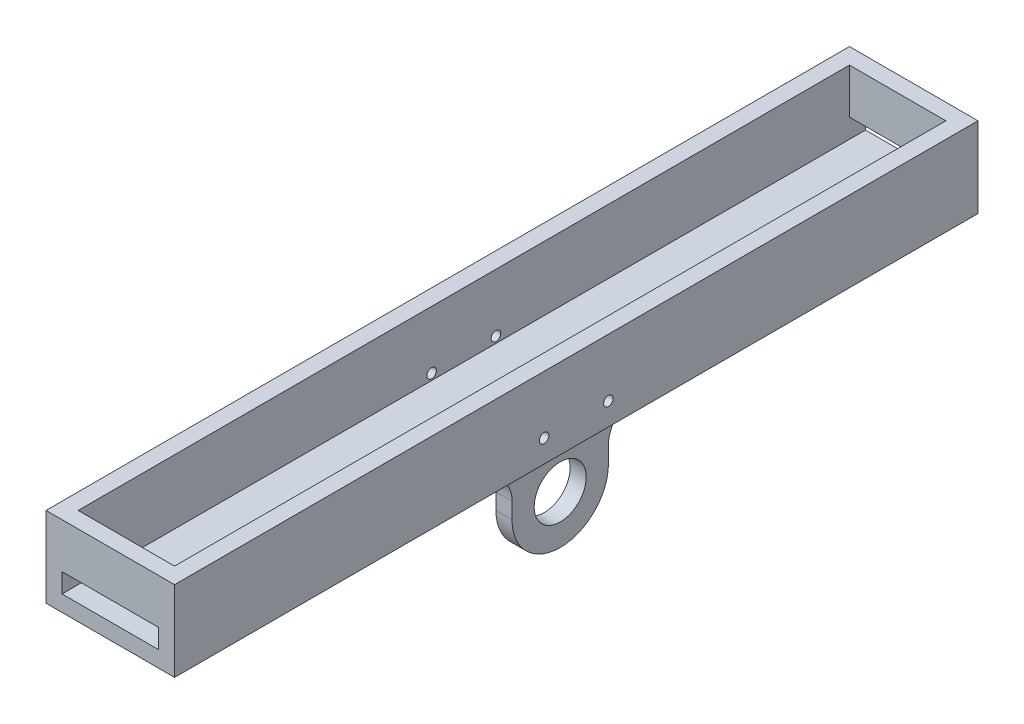
SolidWorks part; units mm, degrees
ref_plane "Front Plane" through (0, 0, 0) normal (0, 0, 1) x (1, 0, 0)
ref_plane "Top Plane" through (0, 0, 0) normal (0, 1, 0) x (1, 0, 0)
ref_plane "Right Plane" through (0, 0, 0) normal (1, 0, 0) x (0, 0, -1)
sketch "Sketch1" plane through (0, 0, 0) normal (0, 0, 1) x (1, 0, 0)
  line L0 (35, 25) -> (40, 25)
  line L1 (0, 0) -> (40, 0)
  line L2 (0, 0) -> (0, 25)
  line L3 (0, 25) -> (5, 25)
  line L4 (40, 0) -> (40, 25)
  line L6 (5, 25) -> (5, 5)
  line L7 (5, 5) -> (35, 5)
  line L8 (35, 25) -> (35, 5)
  dimension "D1" = 30
  dimension "D2" = 5
  dimension "D3" = 5
  dimension "D4" = 5
  dimension "D5" = 20
extrude "Boss-Extrude1" add sketch "Sketch1" along normal blind 250
sketch "Sketch2" plane through (40, 0, 0) normal (1, 0, 0) x (0, 0, -1)
  line L5 (-250, 0) -> (0, 0) construction
  line L6 (-140, -15) -> (-140, -10)
  line L7 (-110, -15) -> (-110, -10)
  line L10 (-150, 0) -> (-100, 0)
  circle A0 centre (-125, -15) radius 8.1
  arc A1 (-140, -15) -> (-110, -15) centre (-125, -15) ccw
  arc A2 (-110, -10) -> (-100, 0) centre (-100, -10) cw
  arc A3 (-140, -10) -> (-150, 0) centre (-150, -10) ccw
  point P4 (-125, 0)
  point P11 (-85, 0)
  point P14 (-115, 0)
  dimension "D2" = 16.2
  dimension "D3" = 10
  dimension "D4" = 15
  dimension "D1" = 15
  dimension "D5" = 50
sketch "Sketch3" plane through (40, 0, 0) normal (1, 0, 0) x (0, 0, -1)
  line L0 (-250, 0) -> (0, 0) construction
  line L1 (-225, 0) -> (-215, 0)
  line L2 (-225, 0) -> (-225, -10)
  line L3 (-225, -10) -> (-215, -10)
  line L4 (-215, 0) -> (-215, -10)
  line L5 (-250, 0) -> (-250, 25) construction
  circle A0 centre (-220, -5) radius 1.75
  dimension "D2" = 3.5
  dimension "D1" = 5
  dimension "D3" = 5
  dimension "D4" = 10
  dimension "D5" = 10
  dimension "D6" = 25
extrude "Boss-Extrude3" add sketch "Sketch3" along normal blind 7 from offset 25.1 offset against normal yes
fillet "Fillet1" radius 5 2 edges at (18.4, -10, 215) (18.4, -10, 225)
sketch "Sketch5" plane through (0, 5, 0) normal (0, 1, 0) x (1, 0, 0)
  line L0 (35, -250) -> (5, -250) construction
  line L1 (5, -125) -> (35, -125) construction
  line L2 (5, -250) -> (5, 0) construction
  line L3 (35, -250) -> (35, 0) construction
  circle A0 centre (20, -230) radius 1.5
  circle A1 centre (20, -210) radius 1.5
  circle A2 centre (20, -40) radius 1.5
  circle A3 centre (20, -20) radius 1.5
  point P8 (20, -250)
  dimension "D3" = 3
  dimension "D1" = 20
  dimension "D2" = 20
extrude "Cut-Extrude1" cut sketch "Sketch5" against normal blind 7
sketch "Sketch6" plane through (0, 25, 0) normal (0, 1, 0) x (1, 0, 0)
  line L0 (35, -250) -> (35, 0) construction
  line L1 (5, 0) -> (35, 0)
  line L2 (5, 0) -> (5, -5)
  line L3 (5, -5) -> (35, -5)
  line L4 (35, 0) -> (35, -5)
  line L5 (35, -250) -> (35, 0) construction
  line L6 (5, -250) -> (35, -250)
  line L7 (5, -250) -> (5, -245)
  line L8 (5, -245) -> (35, -245)
  line L9 (35, -250) -> (35, -245)
  dimension "D1" = 5
  dimension "D2" = 5
extrude "Boss-Extrude4" add sketch "Sketch6" against normal blind 14
extrude "Boss-Extrude5" add sketch "Sketch2" against normal blind 5 from offset 5 offset against normal yes
extrude "Boss-Extrude6" add sketch "Sketch2<3>" along normal blind 5 from offset 35 offset against normal yes
sketch "Sketch2<3>" plane through (40, 0, 0) normal (1, 0, 0) x (0, 0, -1) same geometry as "Sketch2"
sketch "Sketch7" plane through (0, 0, 0) normal (-1, 0, 0) x (0, 0, 1)
  line L0 (250, 25) -> (0, 25) construction
  circle A0 centre (115, 7) radius 1.5
  circle A1 centre (135, 7) radius 1.5
  circle A2 centre (125, -15) radius 8.1 construction
  dimension "D1" = 3
  dimension "D2" = 3
  dimension "D3" = 20
  dimension "D4" = 10
  dimension "D5" = 18
extrude "Cut-Extrude2" cut sketch "Sketch7" against normal through all
